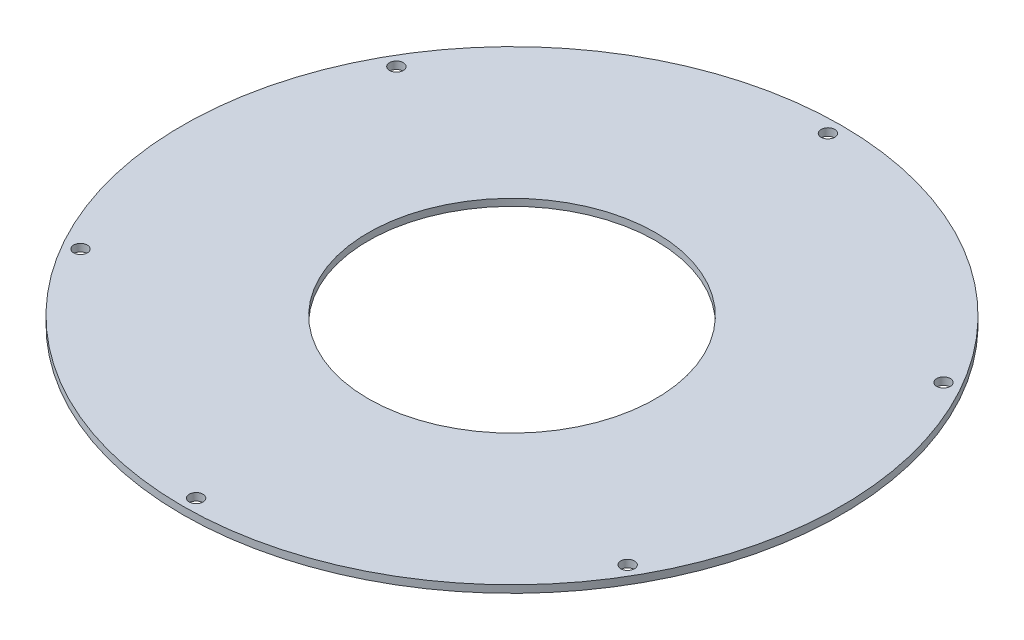
SolidWorks part; units mm, degrees
ref_plane "Front Plane" through (0, 0, 0) normal (0, 0, 1) x (1, 0, 0)
ref_plane "Top Plane" through (0, 0, 0) normal (0, 1, 0) x (1, 0, 0)
ref_plane "Right Plane" through (0, 0, 0) normal (1, 0, 0) x (0, 0, -1)
sketch "Sketch1" plane through (0, 0, 0) normal (0, 1, 0) x (1, 0, 0)
  line L0 (0, 70.8759) -> (0, 65) construction
  line L1 (0, 57) -> (0, 30.925) construction
  line L2 (0, -57) -> (0, -30.925) construction
  circle A0 centre (0, 0) radius 67.5 construction
  circle A1 centre (0, 67.938) radius 1.4732
  circle A2 centre (58.836, 33.969) radius 1.4732
  circle A3 centre (58.836, -33.969) radius 1.4732
  circle A4 centre (0, -67.938) radius 1.4732
  circle A5 centre (-58.836, -33.969) radius 1.4732
  circle A6 centre (-58.836, 33.969) radius 1.4732
  circle A7 centre (0, 0) radius 65
  circle A8 centre (0, 0) radius 70.8759
  circle A9 centre (0, 67.938) radius 2.3241 construction
  circle A10 centre (0, 0) radius 57
  circle A11 centre (0, 0) radius 30.925
  circle A12 centre (-76.2, 0) radius 2.3241 construction
  circle A13 centre (76.2, 0) radius 2.3241 construction
  circle A14 centre (0, 0) radius 76.2 construction
  point P17 (0, 0)
  point P43 (0, 0)
  dimension "D2" = 2.9464
  dimension "D5" = 130
  dimension "D7" = 4.6482
  dimension "D9" = 61.85
  dimension "D6" = 4.6482
  dimension "D8" = 8
  dimension "D10" = 152.4
  dimension "D11" = 76.2
  dimension "D12" = 5.3241
  dimension "D3" = 6
extrude "Boss-Extrude1" add sketch "Sketch1" along normal blind 1.6 contours A8 A1 A2 A3 A4 A5 A6 A7 | A7 A10 | A10 A11 region at (-63.1615, 0, 0) region at (-68.8712, 0, 0) region at (-55.3878, 0, 0)
extrude "Cut-Extrude1" cut sketch "Sketch1<3>" along normal blind 0.1 contours A7 A10 | A10 A11 region at (-63.1615, 0, 0) region at (-55.3878, 0, 0)
sketch "Sketch1<3>" plane through (0, 0, 0) normal (0, 1, 0) x (1, 0, 0) same geometry as "Sketch1"
equation "\"D2@Sketch1\"=0.1160in"
equation "\"D11@Sketch1\"=\"D10@Sketch1\"/2"
equation "\"D12@Sketch1\"=(\"D6@Sketch1\"/2)+3"
